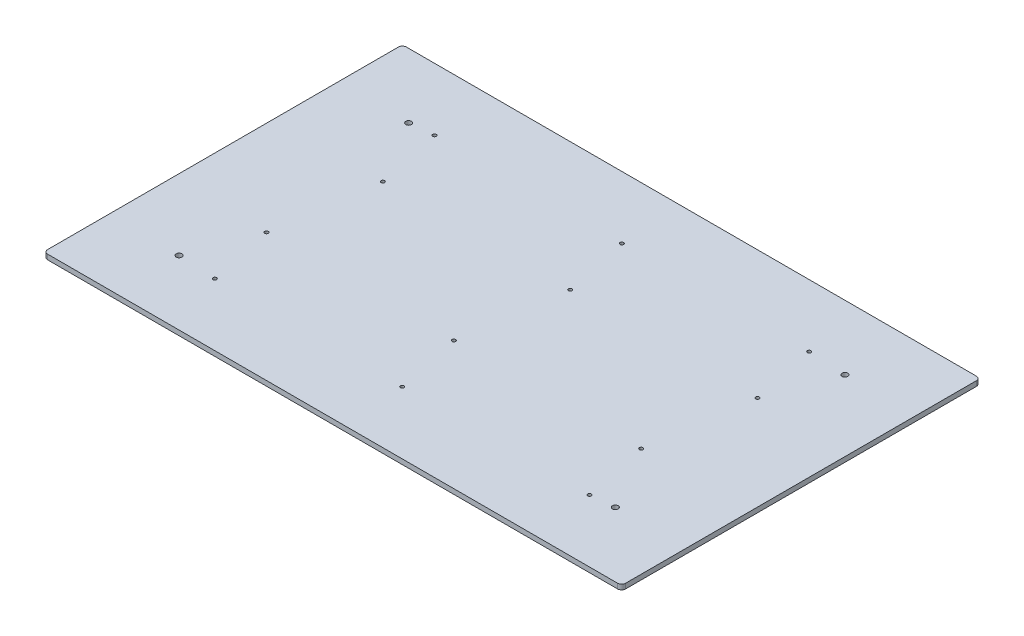
SolidWorks part; units mm, degrees
material "1060 Alloy"
ref_plane "Front" through (0, 0, 0) normal (0, 0, 1) x (1, 0, 0)
ref_plane "Top" through (0, 0, 0) normal (0, 1, 0) x (1, 0, 0)
ref_plane "Right" through (0, 0, 0) normal (1, 0, 0) x (0, 0, -1)
sketch "Sketch1" plane through (0, 0, 0) normal (0, 1, 0) x (1, 0, 0)
  line L1 (-184.15, -114.3) -> (184.15, -114.3)
  line L2 (-184.15, -114.3) -> (-184.15, 114.3)
  line L3 (-184.15, 114.3) -> (184.15, 114.3)
  line L4 (184.15, -114.3) -> (184.15, 114.3)
  line L5 (-184.15, -114.3) -> (184.15, 114.3) construction
  line L6 (-184.15, 114.3) -> (184.15, -114.3) construction
  point P0 (0, 0)
  dimension "D1" = 368.3
  dimension "D2" = 228.6
extrude "Boss-Extrude1" add sketch "Sketch1" along normal blind 3.175
hole_wizard "#6 Clearance Hole1" positions "Sketch2" profile "Sketch3" hole size "#6" standard "ANSI Inch" end condition through all
sketch "Sketch2" plane through (0, 0, 0) normal (0, -1, 0) x (-1, 0, 0)
  point P0 (-139.0015, 73.152)
  point P3 (139.0015, 73.152)
  point P6 (139.0015, -73.152)
  point P9 (-139.0015, -73.152)
sketch "Sketch3" plane through (139.0015, 0, -73.152) normal (1, 0, 0) x (0, 0, -1)
  line L0 (0, 0) -> (0, 3.175)
  line L1 (0, 3.175) -> (1.8288, 3.175)
  line L2 (1.8288, 3.175) -> (1.8288, 0)
  line L5 (1.8288, 0) -> (0, 0)
  line L11 (0, -6.35) -> (0, 107.95) construction
  dimension "Thru Hole Dia." = 3.6576
  dimension "Thru Hole Depth" = 3.175
hole_wizard "Tap Drill for #4-40 Tap1" positions "Sketch4" profile "Sketch5" hole size "#4-40" standard "ANSI Inch" end condition through all
sketch "Sketch4" plane through (0, 0, 0) normal (0, -1, 0) x (-1, 0, 0)
  point P0 (-114.8474, 74.5473)
  point P3 (-123.9126, 32.5137)
  point P6 (4.5326, 74.5473)
  point P9 (-4.5326, 32.5137)
  point P12 (123.9126, 74.5473)
  point P15 (114.8474, 32.5137)
  point P18 (123.9126, -32.5137)
  point P21 (114.8474, -74.5473)
  point P24 (4.5326, -32.5137)
  point P27 (-4.5326, -74.5473)
  point P30 (-114.8474, -32.5137)
  point P33 (-123.9126, -74.5473)
sketch "Sketch5" plane through (114.8474, 0, -74.5473) normal (1, 0, 0) x (0, 0, -1)
  line L0 (0, 0) -> (0, 3.175)
  line L1 (0, 3.175) -> (1.1303, 3.175)
  line L2 (1.1303, 3.175) -> (1.1303, 0)
  line L5 (1.1303, 0) -> (0, 0)
  line L11 (0, -6.35) -> (0, 107.95) construction
  dimension "Thru Hole Dia." = 2.2606
  dimension "Thru Hole Depth" = 3.175
fillet "Fillet1" radius 2.54 4 edges at (184.15, 1.5875, -114.3) (-184.15, 1.5875, -114.3) (-184.15, 1.5875, 114.3) (184.15, 1.5875, 114.3)
